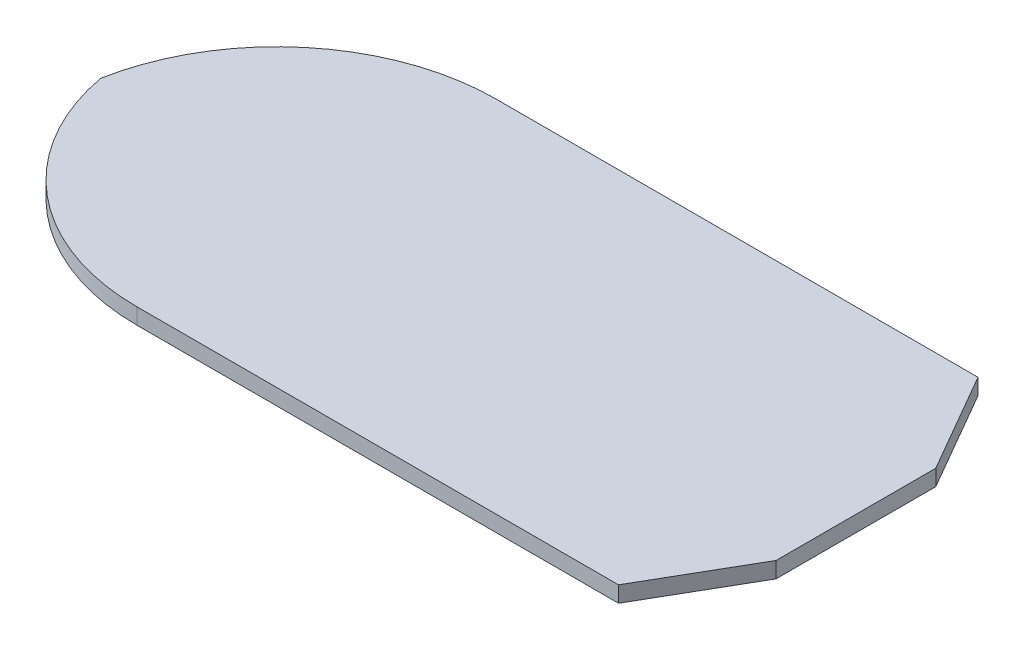
SolidWorks part; units mm, degrees
ref_plane "Plan de face" through (0, 0, 0) normal (0, 0, 1) x (1, 0, 0)
ref_plane "Plan de dessus" through (0, 0, 0) normal (0, 1, 0) x (1, 0, 0)
ref_plane "Plan de droite" through (0, 0, 0) normal (1, 0, 0) x (0, 0, -1)
sketch "Esquisse1" plane through (0, 0, 0) normal (0, 1, 0) x (1, 0, 0)
  line L1 (-95, -45) -> (95, -45)
  line L2 (-95, -45) -> (-95, 45)
  line L3 (-95, 45) -> (95, 45)
  line L4 (95, -45) -> (95, 45)
  line L5 (-95, -45) -> (95, 45) construction
  line L6 (-95, 45) -> (95, -45) construction
  point P0 (0, 0)
  dimension "D1" = 190
  dimension "D2" = 90
extrude "Boss.-Extru.1" add sketch "Esquisse1" along normal blind 4 contours L3 L4 L1 L2
fillet "Congé1" radius 55 2 edges at (-95, 2, 45) (-95, 2, -45)
chamfer "Chanfrein1" distance 25 angle 30 2 edges at (95, 2, 45) (95, 2, -45) first distance on face at (95, 2, 0)
